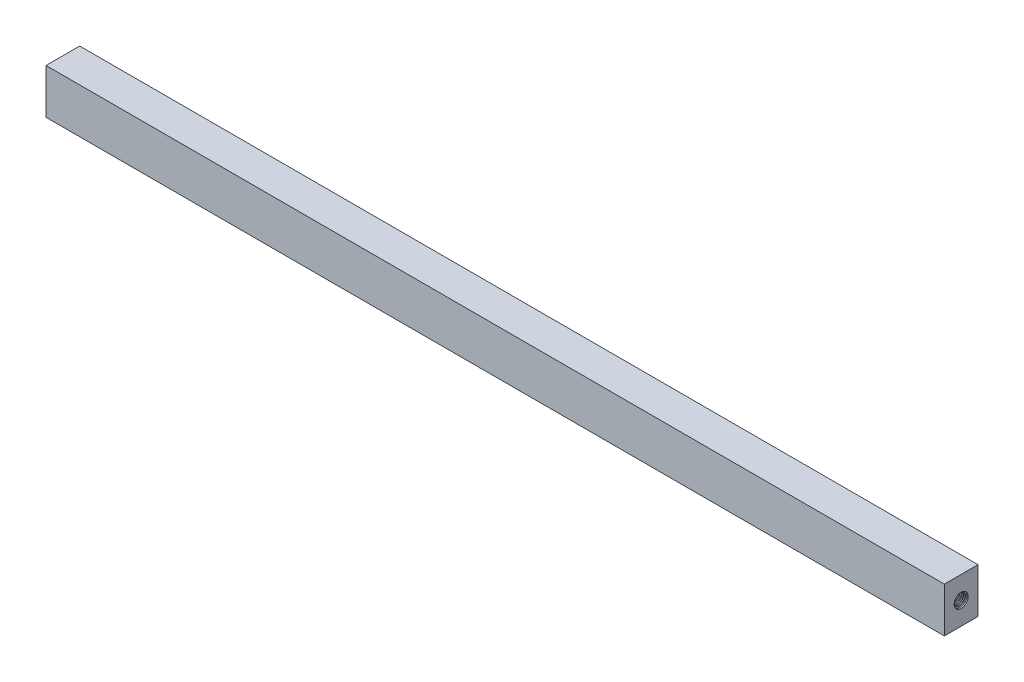
SolidWorks part; units mm, degrees
ref_plane "Front Plane" through (0, 0, 0) normal (0, 0, 1) x (1, 0, 0)
ref_plane "Top Plane" through (0, 0, 0) normal (0, 1, 0) x (1, 0, 0)
ref_plane "Right Plane" through (0, 0, 0) normal (1, 0, 0) x (0, 0, -1)
sketch "Sketch1" plane through (0, 0, 0) normal (0, 0, 1) x (1, 0, 0)
  line L1 (0, 0) -> (508, 0)
  line L2 (0, 0) -> (0, 25.4)
  line L3 (0, 25.4) -> (508, 25.4)
  line L4 (508, 0) -> (508, 25.4)
  dimension "D1" = 508
  dimension "D2" = 25.4
extrude "Boss-Extrude1" add sketch "Sketch1" against normal blind 19.05
sketch "Sketch2" plane through (508, 0, 0) normal (1, 0, 0) x (0, 0, -1)
  line L0 (19.05, 0) -> (19.05, 25.4) construction
  line L1 (19.05, 25.4) -> (0, 25.4) construction
  circle A0 centre (9.525, 12.7) radius 3.9687
  dimension "D3" = 7.9375
  dimension "D1" = 9.525
  dimension "D2" = 12.7
extrude "Cut-Extrude1" cut sketch "Sketch2" against normal blind 25.4
thread "Thread1" pitch 1.0583 method extrude profile "Thread Profile1" start angle 0, offset 0, length 25.4, pitch 1.0583, diameter 7.9375
ref_plane "Plane1" through (508, 12.7, -5.5563) normal (0, -1, 0) x (0, 0, 1)
sketch "Thread Profile1" plane through (508, 12.7, -5.5563) normal (0, -1, 0) x (0, 0, 1)
  line L0 (0, 0) -> (0, 1.0583) construction
  line L11 (0, 0) -> (0, 0.926)
  line L12 (0, 0.926) -> (-0.5728, 0.5953)
  line L13 (-0.5728, 0.5953) -> (-0.5728, 0.3307)
  line L15 (-0.5728, 0.3307) -> (0, 0)
  line L17 (-0.5728, 0.463) -> (0, 0.463) construction
  point P2 (0, 0)
  dimension "Pitch" = 1.0583
  dimension "Profile_Angle" = 60
  dimension "Profile_Land" = 0.2646
  dimension "Profile_Height" = 0.5728
